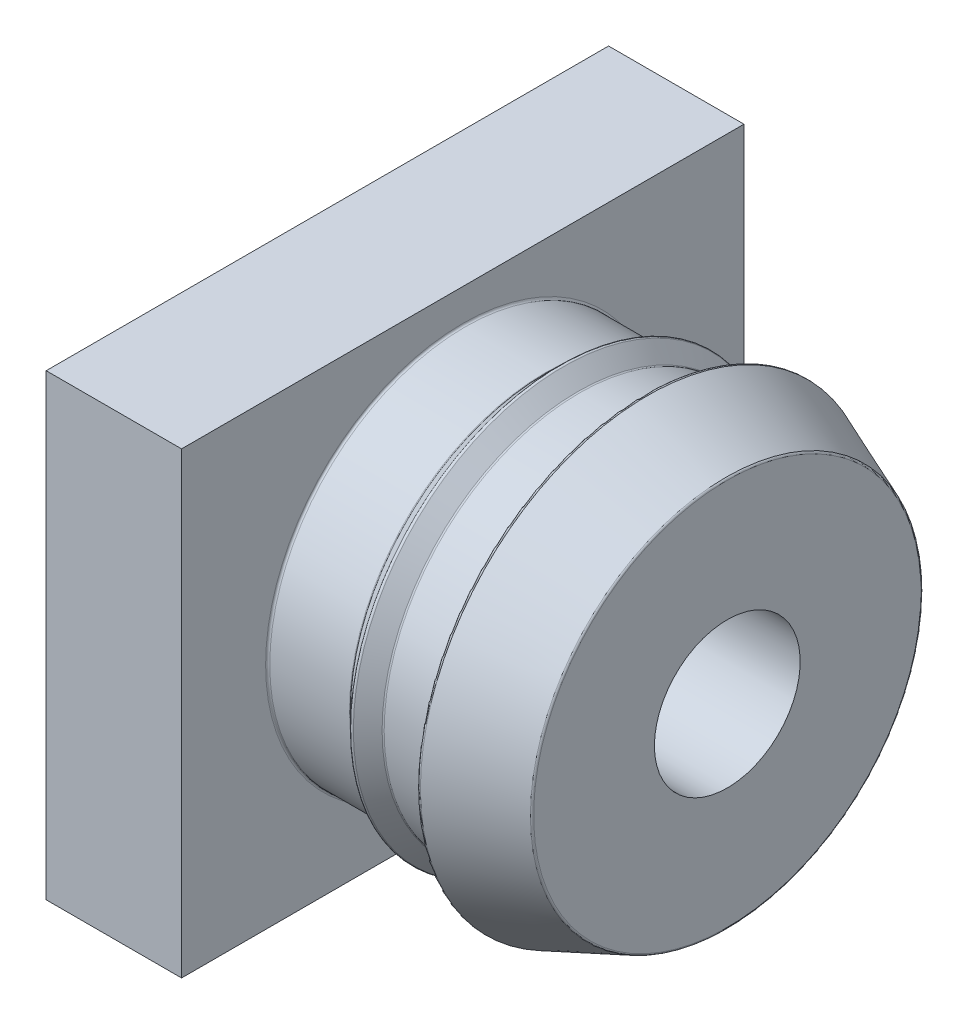
SolidWorks part; units mm, degrees
note: The reader was unsure of these and kept them because the rebuilt part matched: shared geometry of "Sketch2<3>", "Sketch2<4>", "Sketch2<5>", "Sketch2<6>".
ref_plane "Front Plane" through (0, 0, 0) normal (0, 0, 1) x (1, 0, 0)
ref_plane "Top Plane" through (0, 0, 0) normal (0, 1, 0) x (1, 0, 0)
ref_plane "Right Plane" through (0, 0, 0) normal (1, 0, 0) x (0, 0, -1)
sketch "Sketch1" plane through (0, 0, 0) normal (0, 1, 0) x (1, 0, 0)
  line L0 (0, 0) -> (-12.7, 0)
  line L1 (0, 0) -> (0, 9.365)
  line L2 (0, 9.365) -> (-3.97, 10.955)
  line L3 (-3.97, 10.955) -> (-3.97, 9.365)
  line L4 (0, 9.365) -> (-19.3321, 9.365) construction
  line L5 (-3.97, 9.365) -> (-7.15, 9.365)
  line L6 (-7.15, 9.365) -> (-7.94, 10.155)
  line L7 (-7.94, 10.155) -> (-8.73, 9.365)
  line L8 (-8.73, 9.365) -> (-12.7, 9.365)
  line L9 (-12.7, 9.365) -> (-12.7, 0)
  dimension "D1" = 12.7
  dimension "D2" = 9.365
  dimension "D3" = 1.59
  dimension "D4" = 3.97
  dimension "D5" = 7.94
  dimension "D6" = 0.79
revolve "Revolve1" add sketch "Sketch1" angle 360 about L0
sketch "Sketch2" plane through (-12.7, 0, 0) normal (-1, 0, 0) x (0, 0, 1)
  line L0 (0.92, 2.735) -> (0.92, -1.615)
  line L1 (-8.59, 6.425) -> (8.59, 6.425) construction
  line L2 (-8.59, 6.425) -> (-8.59, -6.425) construction
  line L3 (-8.59, -6.425) -> (8.59, -6.425) construction
  line L4 (8.59, 6.425) -> (8.59, -6.425) construction
  line L5 (-8.59, 6.425) -> (8.59, -6.425) construction
  line L6 (-8.59, -6.425) -> (8.59, 6.425) construction
  line L7 (0.92, -1.615) -> (-1.54, -1.615)
  line L8 (-1.54, -1.615) -> (-1.54, 2.735)
  line L9 (-1.54, 2.735) -> (0.92, 2.735)
  line L10 (0, 6.425) -> (0, -6.425) construction
  line L11 (13.5, 11) -> (-13.5, 11)
  line L12 (13.5, 11) -> (13.5, -11)
  line L13 (13.5, -11) -> (-13.5, -11)
  line L14 (-13.5, 11) -> (-13.5, -11)
  line L15 (13.5, 11) -> (-13.5, -11) construction
  line L16 (13.5, -11) -> (-13.5, 11) construction
  line L18 (-8.59, -6.425) -> (8.59, -6.425)
  line L19 (-8.59, -6.425) -> (-8.59, -4.625)
  line L20 (-8.59, -4.625) -> (8.59, -4.625)
  line L21 (8.59, -6.425) -> (8.59, -4.625)
  line L22 (-8.59, -6.425) -> (8.59, -4.625) construction
  line L23 (-8.59, -4.625) -> (8.59, -6.425) construction
  line L28 (-9.29, 6.625) -> (9.29, 6.625)
  line L29 (-9.29, 6.625) -> (-9.29, -7.425)
  line L30 (-9.29, -7.425) -> (9.29, -7.425)
  line L31 (9.29, 6.625) -> (9.29, -7.425)
  line L32 (-9.29, 6.625) -> (9.29, -7.425) construction
  line L33 (-9.29, -7.425) -> (9.29, 6.625) construction
  circle A0 centre (-6.19, 3.935) radius 0.9
  circle A1 centre (6.19, 3.935) radius 0.9
  circle A2 centre (0, 0) radius 3.5
  point P0 (0, 0)
  point P8 (0, 0)
  point P25 (0, -5.525)
  point P35 (0, -0.4)
  circle M5 centre (0, 0) radius 9.365
  dimension "D9" = 1.8
  dimension "D10" = 2.49
  dimension "D11" = 2.4
  dimension "D12" = 7
  dimension "D1" = 12.85
  dimension "D2" = 17.18
  dimension "D3" = 7.67
  dimension "D4" = 3.69
  dimension "D5" = 2.46
  dimension "D6" = 4.35
  dimension "D7" = 22
  dimension "D8" = 27
  dimension "D13" = 1.8
  dimension "D14" = 0.7
  dimension "D15" = 0.7
  dimension "D16" = 0.2
  dimension "D17" = 1
extrude "Boss-Extrude1" add sketch "Sketch2" along normal blind 1.5
extrude "Boss-Extrude2" add sketch "Sketch2<3>" along normal offset from surface (2 mm away) 0.5 contours L20 L18 M5 | L18 L21 L20 M5 | L20 L19 L18 M5 up to face at (-14.2, 0, 0) offset beyond the face yes
sketch "Sketch2<3>" plane through (-12.7, 0, 0) normal (-1, 0, 0) x (0, 0, 1) same geometry as "Sketch2"
extrude "Boss-Extrude3" add sketch "Sketch2<4>" along normal offset from surface (5 mm away) 3.5 contours A1 | A0 up to face at (-14.2, -5.525, 0) offset beyond the face yes
sketch "Sketch2<4>" plane through (-12.7, 0, 0) normal (-1, 0, 0) x (0, 0, 1) same geometry as "Sketch2"
extrude "Cut-Extrude1" cut sketch "Sketch2<5>" against normal through all contours A2 L8 L9 L0 L7 | L9 L8 L7 L0
sketch "Sketch2<5>" plane through (-12.7, 0, 0) normal (-1, 0, 0) x (0, 0, 1) same geometry as "Sketch2"
extrude "Boss-Extrude4" add sketch "Sketch2<6>" along normal offset from surface (6.5 mm away) 5 contours L11 L14 L13 L12 L28 L31 L30 L29 M5 | L30 M5 | L31 M5 | L29 M5 | L28 M5
sketch "Sketch2<6>" plane through (-12.7, 0, 0) normal (-1, 0, 0) x (0, 0, 1) same geometry as "Sketch2"
fillet "Fillet1" radius 0.1 7 edges at (-12.7, 0, 9.365) (-8.73, 0, -9.365) (-7.15, 0, -9.365) (-7.94, 0, -10.155) (-3.97, 0, -9.365) (-3.97, 0, -10.955) (0, 0, -9.365)
fillet "Fillet4" radius 0.2 2 edges at (-17.7, 3.935, -5.29) (-17.7, 3.935, 7.09)
fillet "Fillet5" radius 0.2 4 edges at (-14.7, -5.525, -8.59) (-14.7, -6.425, 0) (-14.7, -5.525, 8.59) (-14.7, -4.625, 0)
ref_plane "Plane1" through (0, 3.5, 0) normal (0, -1, 0) x (-1, 0, 0)
ref_plane "Plane2" through (0, 0, 0) normal (0, 0, -1) x (-1, 0, 0)
sketch "Sketch6" plane through (-19.2, 0, 0) normal (-1, 0, 0) x (0, 0, 1)
  line L0 (-9.29, 6.625) -> (-9.29, -7.425) construction
  line L1 (-9.29, 8.625) -> (9.29, 8.625)
  line L2 (-11.29, 6.625) -> (-11.29, -6.425)
  line L3 (-9.29, -8.425) -> (9.29, -8.425)
  line L4 (11.29, 6.625) -> (11.29, -6.425)
  line L5 (-11.29, 8.625) -> (11.29, -8.425) construction
  line L6 (-11.29, -8.425) -> (11.29, 8.625) construction
  line L8 (9.29, 6.625) -> (9.29, -7.425) construction
  line L10 (-9.29, -7.425) -> (9.29, -7.425) construction
  line L11 (-9.29, 6.625) -> (9.29, 6.625) construction
  arc A0 (9.29, -8.425) -> (11.29, -6.425) centre (9.29, -6.425) ccw
  arc A1 (9.29, 8.625) -> (11.29, 6.625) centre (9.29, 6.625) cw
  arc A2 (-9.29, 8.625) -> (-11.29, 6.625) centre (-9.29, 6.625) ccw
  arc A3 (-11.29, -6.425) -> (-9.29, -8.425) centre (-9.29, -6.425) ccw
  point P4 (0, 0.1)
  dimension "D5" = 2
  dimension "D1" = 2
  dimension "D2" = 1
  dimension "D3" = 2
  dimension "D4" = 2
sweep "Cut-Sweep1" cut path "Sketch6" circular profile diameter 1.778 parameters "D3"=1.778
fillet "Fillet6" radius 0.2 2 edges at (-14.2, 3.935, -5.29) (-14.2, 3.935, 7.09)
sketch "Sketch8" plane through (0, 0, 0) normal (0, 0, 1) x (1, 0, 0)
  line L0 (-17.9, -11) -> (-17.9, -9.8342)
  line L1 (-19.2, -11) -> (-12.7, -11) construction
  line L2 (-17.9, -9.8342) -> (-15.4, -11)
  line L3 (-15.4, -11) -> (-17.9, -11)
  line L4 (-19.2, 11) -> (-19.2, -11) construction
  dimension "D1" = 65
  dimension "D2" = 2.5
  dimension "D3" = 1.3
extrude "Cut-Extrude2" cut sketch "Sketch8" against normal blind 7 and the other way blind 7
equation "\"WallThick\"= 1.2'thickness of wall for printer"
equation "\"dHole\"= 3.3'diameter of screw hole"
equation "\"D3@Sketch4\"=\"WallThick\"*2+\"dHole\""
